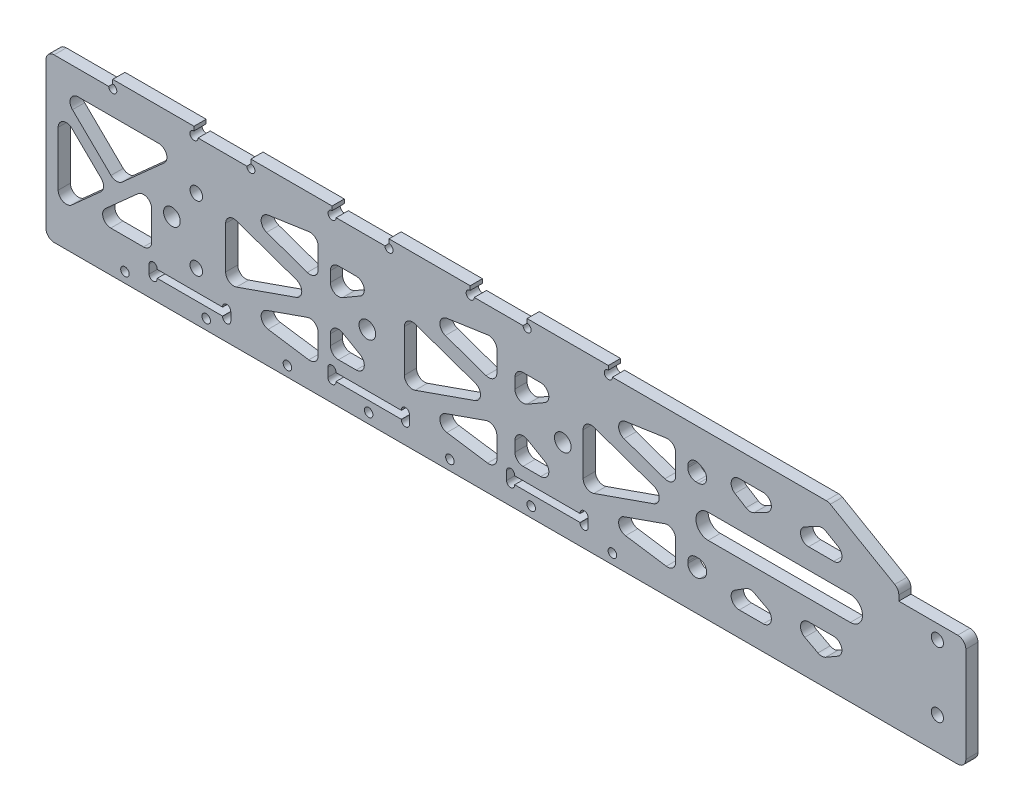
SolidWorks part; units mm, degrees
material "Thornel Mat VMA"
ref_plane "前视基准面" through (0, 0, 0) normal (0, 0, 1) x (1, 0, 0)
ref_plane "上视基准面" through (0, 0, 0) normal (0, 1, 0) x (1, 0, 0)
ref_plane "右视基准面" through (0, 0, 0) normal (1, 0, 0) x (0, 0, -1)
sketch "草图1" plane through (0, 0, 0) normal (0, 0, 1) x (1, 0, 0)
  line L1 (-137.215, -20) -> (137.215, -20)
  line L2 (-137.215, -20) -> (-137.215, 20)
  line L3 (-137.215, 20) -> (137.215, 20)
  line L4 (137.215, -20) -> (137.215, 20)
  line L5 (-137.215, -20) -> (137.215, 20) construction
  line L6 (-137.215, 20) -> (137.215, -20) construction
  point P0 (0, 0)
  dimension "D1" = 274.43
  dimension "D2" = 40
extrude "凸台-拉伸1" add sketch "草图1" along normal blind 3
sketch "草图2" plane through (0, 0, 0) normal (0, 0, 1) x (1, 0, 0)
  line L0 (-157.1827, 0) -> (155.6526, 0) construction
  line L1 (-137.215, -20) -> (-153.215, -20)
  line L2 (-137.215, -20) -> (-137.215, 7.5)
  line L3 (-137.215, 7.5) -> (-153.215, 7.5)
  line L4 (-153.215, -20) -> (-153.215, 7.5)
  line L5 (137.215, -20) -> (153.215, -20)
  line L6 (137.215, -20) -> (137.215, 7.5)
  line L7 (137.215, 7.5) -> (153.215, 7.5)
  line L8 (153.215, -20) -> (153.215, 7.5)
  dimension "D1" = 16
  dimension "D2" = 16
  dimension "D3" = 27.5
  dimension "D4" = 27.5
extrude "凸台-拉伸2" add sketch "草图2" along normal blind 3
sketch "草图3" plane through (0, 0, 3) normal (0, 0, 1) x (1, 0, 0)
  line L0 (-137.215, 20) -> (-137.215, 7.5) construction
  line L1 (-212.4147, 0) -> (176.0969, 0) construction
  line L2 (0, -57.7717) -> (0, 69.9209) construction
  line L3 (212.4147, 0) -> (-176.0969, 0) construction
  line L7 (-212.4147, 0) -> (176.0969, 0) construction
  line L8 (212.4147, 0) -> (-176.0969, 0) construction
  circle A0 centre (-146.215, -12) radius 1.5
  circle A1 centre (-146.215, 4) radius 1.5
  circle A4 centre (-102.215, 0) radius 4.5
  circle A7 centre (146.215, 4) radius 1.5
  circle A8 centre (146.215, -12) radius 1.5
  circle A9 centre (114.785, 0) radius 3
  dimension "D1" = 3
  dimension "D2" = 3
  dimension "D7" = 9
  dimension "D9" = 217
  dimension "D8" = 6
  dimension "D3" = 9
  dimension "D4" = 16
  dimension "D5" = 4
  dimension "D6" = 44
extrude "切除-拉伸1" cut sketch "草图3" against normal through all
sketch "草图6" plane through (0, 0, 3) normal (0, 0, 1) x (1, 0, 0)
  line L0 (-137.215, 7.5) -> (-153.215, 7.5) construction
  line L1 (-137.215, 20) -> (-136.715, 20)
  line L2 (-137.215, 20) -> (-137.215, 7.5)
  line L3 (-137.215, 7.5) -> (-136.715, 7.5)
  line L4 (-136.715, 20) -> (-136.715, 7.5)
  line L5 (137.215, 20) -> (136.715, 20)
  line L6 (137.215, 20) -> (137.215, 7.5)
  line L7 (137.215, 7.5) -> (136.715, 7.5)
  line L8 (136.715, 20) -> (136.715, 7.5)
  line L9 (153.215, 7.5) -> (137.215, 7.5) construction
  dimension "D1" = 0.5
  dimension "D2" = 0.5
  dimension "D3" = 0
  dimension "D4" = 0
extrude "切除-拉伸4" cut sketch "草图6" against normal blind 10
sketch "草图13" plane through (0, 0, 3) normal (0, 0, 1) x (1, 0, 0)
  line L0 (89.785, 0) -> (124.785, 0) construction
  line L1 (89.785, 3) -> (124.785, 3)
  line L2 (89.785, -3) -> (124.785, -3)
  arc A0 (89.785, 3) -> (89.785, -3) centre (89.785, 0) ccw
  arc A1 (124.785, -3) -> (124.785, 3) centre (124.785, 0) ccw
  circle A2 centre (114.785, 0) radius 3 construction
  point P3 (107.285, 0)
  dimension "D1" = 3
  dimension "D2" = 10
  dimension "D3" = 25
extrude "切除-拉伸10" cut sketch "草图13" against normal blind 10
sketch "草图14" plane through (0, 0, 3) normal (0, 0, 1) x (1, 0, 0)
  line L0 (-73.215, 20) -> (-73.215, -20)
  line L1 (136.715, 20) -> (-136.715, 20) construction
  line L2 (-153.215, -20) -> (153.215, -20) construction
  line L3 (-73.215, -20) -> (-153.215, -20)
  line L4 (-153.215, -20) -> (-153.215, 20)
  line L5 (-153.215, 20) -> (-73.215, 20)
  dimension "D1" = 80
extrude "切除-拉伸11" cut sketch "草图14" against normal blind 10
sketch "草图15" plane through (0, 0, 3) normal (0, 0, 1) x (1, 0, 0)
  line L0 (-62.2235, 0) -> (39.7809, 0) construction
  line L1 (-73.215, -20) -> (153.215, -20) construction
  line L2 (-73.215, -20) -> (-73.215, 20) construction
  line L3 (0, 0) -> (0, -20) construction
  line L4 (5.8925, 0) -> (5.8925, -4.9483) construction
  circle A0 centre (-42.215, 0) radius 2.05
  circle A1 centre (0, 0) radius 2.05 construction
  circle A4 centre (54, 0) radius 2.05
  circle A5 centre (5.8925, 0) radius 2.05
  dimension "D2" = 4.1
  dimension "D5" = 4.1
  dimension "D1" = 20
  dimension "D3" = 31
  dimension "D4" = 54
extrude "切除-拉伸12" cut sketch "草图15" against normal blind 10
sketch "草图16" plane through (0, 0, 0) normal (0, 0, -1) x (-1, 0, 0)
  circle A0 centre (-66.215, -17.5) radius 1.05
  circle A1 centre (-46.215, -17.5) radius 1.05
  circle A2 centre (-26.215, -17.5) radius 1.05
  circle A3 centre (-6.215, -17.5) radius 1.05
  circle A4 centre (13.785, -17.5) radius 1.05
  circle A5 centre (33.785, -17.5) radius 1.05
  circle A6 centre (53.785, -17.5) radius 1.05
  dimension "D1" = 2.1
extrude "切除-拉伸13" cut sketch "草图16" against normal blind 10
sketch "草图17" plane through (0, 0, 0) normal (0, 0, -1) x (-1, 0, 0)
  line L0 (-65.215, 20) -> (-65.215, 22)
  line L1 (-136.715, 20) -> (73.215, 20) construction
  line L2 (-65.215, 22) -> (-45.215, 22)
  line L3 (-45.215, 22) -> (-45.215, 20)
  line L4 (-45.215, 20) -> (-65.215, 20)
  line L5 (-75.215, 22) -> (-75.215, 20) construction
  line L6 (-21.215, 22) -> (-21.215, 7.5304) construction
  line L7 (-73.215, 22) -> (30.785, 22) construction
  line L9 (-11.215, 20) -> (-31.215, 20)
  line L10 (-31.215, 20) -> (-31.215, 22)
  line L11 (-31.215, 22) -> (-11.215, 22)
  line L12 (-11.215, 22) -> (-11.215, 20)
  line L13 (2.785, 20) -> (22.785, 20)
  line L14 (2.785, 22) -> (2.785, 20)
  line L15 (22.785, 22) -> (2.785, 22)
  line L16 (22.785, 20) -> (22.785, 22)
  line L17 (36.785, 20) -> (56.785, 20)
  line L18 (56.785, 22) -> (36.785, 22)
  line L19 (36.785, 22) -> (36.785, 20)
  line L20 (56.785, 20) -> (56.785, 22)
  dimension "D1" = 10
  dimension "D2" = 20
  dimension "D3" = 2
  dimension "D5" = 10
  dimension "D6" = 2
  dimension "D7" = 14
  dimension "D4" = 2
extrude "凸台-拉伸3" add sketch "草图17" against normal blind 3
sketch "草图18" plane through (0, 0, 0) normal (0, 0, -1) x (-1, 0, 0)
  line L0 (27.735, -12.95) -> (47.835, -12.95)
  line L1 (-60.265, -12.95) -> (-40.165, -12.95)
  line L2 (-60.265, -12.95) -> (-60.265, -15.05)
  line L3 (-60.265, -15.05) -> (-40.165, -15.05)
  line L4 (-40.165, -12.95) -> (-40.165, -15.05)
  line L5 (-60.265, -12.95) -> (-40.165, -15.05) construction
  line L6 (-60.265, -15.05) -> (-40.165, -12.95) construction
  line L7 (27.735, -15.05) -> (47.835, -15.05)
  line L8 (-40.165, -12.95) -> (-40.165, -15.05) construction
  line L9 (47.835, -12.95) -> (47.835, -15.05)
  line L13 (-16.265, -12.95) -> (3.835, -12.95)
  line L14 (-16.265, -15.05) -> (3.835, -15.05)
  line L15 (3.835, -12.95) -> (3.835, -15.05)
  line L16 (-16.265, -12.95) -> (-16.265, -15.05)
  line L17 (27.735, -12.95) -> (27.735, -15.05)
  point P0 (-50.215, -14)
  dimension "D2" = 44
extrude "切除-拉伸14" cut sketch "草图18" against normal through all
sketch "草图19" plane through (0, 0, 0) normal (0, 0, -1) x (-1, 0, 0)
  line L0 (-40.165, -12.95) -> (-60.265, -12.95) construction
  line L1 (-60.265, -15.05) -> (-40.165, -15.05) construction
  circle A0 centre (-59.265, -12.95) radius 1
  circle A1 centre (-59.265, -15.05) radius 1
  circle A2 centre (-41.165, -12.95) radius 1
  circle A3 centre (-41.165, -15.05) radius 1
  circle A4 centre (-15.265, -12.95) radius 1
  circle A5 centre (-15.265, -15.05) radius 1
  circle A6 centre (2.835, -12.95) radius 1
  circle A7 centre (2.835, -15.05) radius 1
  circle A8 centre (28.735, -12.95) radius 1
  circle A9 centre (28.735, -15.05) radius 1
  circle A10 centre (46.835, -12.95) radius 1
  circle A11 centre (46.835, -15.05) radius 1
  dimension "D1" = 2
  dimension "D3" = 44
  dimension "D2" = 3
extrude "切除-拉伸15" cut sketch "草图19" against normal blind 3
chamfer "倒角1" distance 10 angle 60 1 edges at (136.715, 20, 1.5) first distance on face at (136.715, 13.75, 1.5)
sketch "草图21" plane through (0, 0, 0) normal (0, 0, -1) x (-1, 0, 0)
  line L0 (-86.785, 0) -> (73.215, 0) construction
  line L1 (73.215, 20) -> (73.215, -20) construction
  line L8 (-63.8825, -14) -> (-59, -8) construction
  line L15 (-81.785, 14) -> (-59, 14) construction
  line L16 (-81.785, 14) -> (-81.785, -14) construction
  line L18 (-81.785, -14) -> (-59, -14) construction
  line L19 (-59, 14) -> (-59, -14) construction
  line L20 (-81.785, 14) -> (-59, -14) construction
  line L21 (-81.785, -14) -> (-59, 14) construction
  line L23 (-63.8825, 14) -> (-59, 8) construction
  line L25 (73.215, -20) -> (-153.215, -20) construction
  line L26 (-59, -8) -> (-81.785, 0)
  line L27 (-81.785, 0) -> (-59, 8)
  line L32 (-61.4412, -11) -> (-81.785, -14)
  line L33 (-81.785, -14) -> (-81.785, -3.8571)
  line L35 (-81.785, 14) -> (-81.785, 3.8571)
  line L36 (-81.785, 3.8571) -> (-61.4412, 11)
  line L39 (-61.4412, 11) -> (-81.785, 14)
  line L41 (-81.785, -3.8571) -> (-61.4412, -11)
  line L43 (-59, -8) -> (-59, 8)
  line L45 (-128.1773, 8) -> (-117.785, 14) construction
  line L46 (-117.785, 14) -> (-84.785, 14) construction
  line L47 (-84.785, 14) -> (-84.785, 8) construction
  line L48 (-84.785, 8) -> (-128.1773, 8) construction
  line L49 (-119.3945, 20) -> (-136.715, 10) construction
  line L50 (-119.3945, 20) -> (-65.215, 20) construction
  line L51 (-128.1773, 8) -> (-117.785, 14)
  line L52 (-117.785, 14) -> (-106.4812, 8)
  line L53 (-106.4812, 8) -> (-128.1773, 8)
  line L54 (-111.3862, 14) -> (-100.0824, 8)
  line L55 (-100.0824, 8) -> (-90.4564, 14)
  line L56 (-90.4564, 14) -> (-111.3862, 14)
  line L57 (-84.785, 14) -> (-94.411, 8)
  line L58 (-94.411, 8) -> (-84.785, 8)
  line L59 (-84.785, 8) -> (-84.785, 14)
  line L60 (-94.411, -8) -> (-84.785, -8)
  line L61 (-84.785, -14) -> (-94.411, -8)
  line L62 (-84.785, -8) -> (-84.785, -14)
  line L63 (-100.0824, -8) -> (-90.4564, -14)
  line L64 (-111.3862, -14) -> (-100.0824, -8)
  line L65 (-90.4564, -14) -> (-111.3862, -14)
  line L66 (-106.4812, -8) -> (-128.1773, -8)
  line L67 (-117.785, -14) -> (-106.4812, -8)
  line L68 (-128.1773, -8) -> (-117.785, -14)
  line L69 (-15, -8) -> (-15, 8)
  line L70 (-37.785, 0) -> (-15, 8)
  line L71 (-15, -8) -> (-37.785, 0)
  line L72 (-17.4413, 11) -> (-37.785, 14)
  line L73 (-37.785, 14) -> (-37.785, 3.8571)
  line L74 (-37.785, 3.8571) -> (-17.4413, 11)
  line L75 (-37.785, -3.8571) -> (-17.4413, -11)
  line L76 (-17.4413, -11) -> (-37.785, -14)
  line L77 (-37.785, -14) -> (-37.785, -3.8571)
  line L78 (29, -8) -> (29, 8)
  line L79 (6.215, 0) -> (29, 8)
  line L80 (29, -8) -> (6.215, 0)
  line L81 (26.5587, 11) -> (6.215, 14)
  line L82 (6.215, 14) -> (6.215, 3.8571)
  line L83 (6.215, 3.8571) -> (26.5587, 11)
  line L84 (6.215, -3.8571) -> (26.5587, -11)
  line L85 (26.5587, -11) -> (6.215, -14)
  line L86 (6.215, -14) -> (6.215, -3.8571)
  line L87 (-56, 10) -> (-42.2187, 2)
  line L88 (-42.2187, 2) -> (-42.2187, 10)
  line L89 (-42.2187, 10) -> (-56, 10)
  line L90 (-42.2187, -2) -> (-42.2187, -10)
  line L91 (-56, -10) -> (-42.2187, -2)
  line L92 (-42.2187, -10) -> (-56, -10)
  line L93 (-45.215, 20) -> (-31.215, 20) construction
  line L94 (3.215, -2) -> (3.215, -10)
  line L95 (3.215, -10) -> (-10.5663, -10)
  line L96 (-10.5663, -10) -> (3.215, -2)
  line L97 (3.215, 10) -> (-10.5663, 10)
  line L98 (-10.5663, 10) -> (3.215, 2)
  line L99 (3.215, 2) -> (3.215, 10)
  line L100 (40.215, 14) -> (55.8771, 0)
  line L101 (55.8771, 0) -> (70.215, 14)
  line L102 (70.215, 14) -> (40.215, 14)
  line L106 (70.215, 9.8071) -> (58.1189, -2.0039)
  line L107 (58.1189, -2.0039) -> (70.215, -12.8164)
  line L108 (70.215, -12.8164) -> (70.215, 9.8071)
  line L109 (56.785, 20) -> (73.215, 20) construction
  line L114 (47.215, 3.719) -> (47.215, -9.95)
  line L115 (47.215, -9.95) -> (62.5068, -9.95)
  line L116 (47.215, 3.719) -> (62.5068, -9.95)
  line L117 (45.835, -12.95) -> (29.735, -12.95) construction
  arc A0 (-89.785, -3) -> (-89.785, 3) centre (-89.785, 0) ccw construction
  circle A1 centre (-54, 0) radius 2.05 construction
  circle A2 centre (42.215, 0) radius 2.05 construction
  point P7 (-70.3925, 0)
  point P93 (63.046, 7)
  dimension "D1" = 5
  dimension "D2" = 5
  dimension "D3" = 6
  dimension "D4" = 6
  dimension "D5" = 6
  dimension "D6" = 8
  dimension "D7" = 6
  dimension "D8" = 3
  dimension "D10" = 3
  dimension "D11" = 3
  dimension "D12" = 3
  dimension "D13" = 44
  dimension "D14" = 4.4337
  dimension "D15" = 3
  dimension "D16" = 8
  dimension "D17" = 10
  dimension "D19" = 3
  dimension "D20" = 3
  dimension "D21" = 6
  dimension "D22" = 30
  dimension "D23" = 3
  dimension "D24" = 5
  dimension "D25" = 3
  dimension "D26" = 3
  dimension "D18" = 2
extrude "切除-拉伸16" cut sketch "草图21" against normal through all
fillet "圆角1" radius 2 66 edges at (81.785, 3.8571, 1.5) (81.785, 14, 1.5) (61.4412, 11, 1.5) (-47.215, -9.95, 1.5) (-47.215, 3.719, 1.5) (-62.5068, -9.95, 1.5) (-3.215, -10, 1.5) (10.5663, -10, 1.5) (-3.215, -2, 1.5) (-55.8771, 0, 1.5) (-40.215, 14, 1.5) (-70.215, 14, 1.5) (-3.215, 10, 1.5) (-3.215, 2, 1.5) (10.5663, 10, 1.5) (-58.1189, -2.0039, 1.5) (-70.215, 9.8071, 1.5) (-70.215, -12.8164, 1.5) (17.4413, -11, 1.5) (37.785, -14, 1.5) (37.785, -3.8571, 1.5) (15, 8, 1.5) (15, -8, 1.5) (37.785, 0, 1.5) (42.2187, 2, 1.5) (56, 10, 1.5) (42.2187, 10, 1.5) (17.4413, 11, 1.5) (37.785, 3.8571, 1.5) (37.785, 14, 1.5) (42.2187, -10, 1.5) (56, -10, 1.5) (42.2187, -2, 1.5) (-29, 8, 1.5) (-29, -8, 1.5) (-6.215, 0, 1.5) (-26.5587, -11, 1.5) (-6.215, -14, 1.5) (-6.215, -3.8571, 1.5) (-26.5587, 11, 1.5) (-6.215, 3.8571, 1.5) (-6.215, 14, 1.5) (81.785, 0, 1.5) (59, 8, 1.5) (59, -8, 1.5) (61.4412, -11, 1.5) (81.785, -14, 1.5) (81.785, -3.8571, 1.5) (106.4812, 8, 1.5) (100.0824, 8, 1.5) (111.3862, 14, 1.5) (90.4564, 14, 1.5) (90.4564, -14, 1.5) (111.3862, -14, 1.5) (100.0824, -8, 1.5) (128.1773, -8, 1.5) (106.4812, -8, 1.5) (117.785, -14, 1.5) (84.785, -8, 1.5) (84.785, -14, 1.5) (94.411, -8, 1.5) (94.411, 8, 1.5) (84.785, 14, 1.5) (84.785, 8, 1.5) (117.785, 14, 1.5) (128.1773, 8, 1.5)
fillet "圆角2" radius 2 6 edges at (-73.215, 20, 1.5) (-73.215, -20, 1.5) (119.3945, 20, 1.5) (136.715, 10, 1.5) (153.215, 7.5, 1.5) (153.215, -20, 1.5)
sketch "草图22" plane through (0, 0, 0) normal (0, 0, -1) x (-1, 0, 0)
  line L0 (36.215, 20) -> (36.215, -12.95) construction
  line L1 (22.785, 20) -> (36.785, 20) construction
  line L2 (45.835, -12.95) -> (29.735, -12.95) construction
  circle A0 centre (42.215, 0) radius 2.05 construction
  circle A1 centre (36.215, 8) radius 1.55
  circle A2 centre (36.215, -8) radius 1.55
  dimension "D2" = 3.1
  dimension "D3" = 3.1
  dimension "D5" = 8
  dimension "D1" = 6
  dimension "D4" = 8
extrude "切除-拉伸17" cut sketch "草图22" against normal blind 10
sketch "草图24" plane through (0, 0, 0) normal (0, 0, -1) x (-1, 0, 0)
  line L0 (-58.265, -12.95) -> (-42.165, -12.95)
  line L1 (-58.265, -12.95) -> (-58.265, -13.05)
  line L2 (-42.165, -12.95) -> (-42.165, -13.05)
  line L3 (-58.265, -13.05) -> (-42.165, -13.05)
  line L4 (-58.265, -15.05) -> (-42.165, -15.05)
  line L5 (-58.265, -15.05) -> (-58.265, -14.95)
  line L6 (-42.165, -15.05) -> (-42.165, -14.95)
  line L7 (-58.265, -14.95) -> (-42.165, -14.95)
  line L8 (-14.265, -12.95) -> (1.835, -12.95)
  line L9 (-14.265, -12.95) -> (-14.265, -13.05)
  line L10 (1.835, -12.95) -> (1.835, -13.05)
  line L11 (-14.265, -13.05) -> (1.835, -13.05)
  line L12 (-14.265, -15.05) -> (1.835, -15.05)
  line L13 (-14.265, -15.05) -> (-14.265, -14.95)
  line L14 (1.835, -15.05) -> (1.835, -14.95)
  line L15 (-14.265, -14.95) -> (1.835, -14.95)
  line L16 (29.735, -12.95) -> (45.835, -12.95)
  line L17 (29.735, -12.95) -> (29.735, -13.05)
  line L18 (45.835, -12.95) -> (45.835, -13.05)
  line L19 (29.735, -13.05) -> (45.835, -13.05)
  line L20 (29.735, -15.05) -> (45.835, -15.05)
  line L21 (29.735, -15.05) -> (29.735, -14.95)
  line L22 (45.835, -15.05) -> (45.835, -14.95)
  line L23 (29.735, -14.95) -> (45.835, -14.95)
  line L24 (29.735, -15.05) -> (45.835, -15.05) construction
  arc A0 (29.735, -12.95) -> (27.735, -12.95) centre (28.735, -12.95) ccw construction
  arc A1 (27.735, -15.05) -> (29.735, -15.05) centre (28.735, -15.05) ccw construction
  dimension "D1" = 0.1
  dimension "D2" = 0.1
  dimension "D3" = 0.1
  dimension "D4" = 0.1
  dimension "D5" = 0.1
  dimension "D6" = 0.1
extrude "凸台-拉伸4" add sketch "草图24" against normal up to surface (3 mm away) up to face at (-37.765, 8, 3)
sketch "草图25" plane through (0, 0, 0) normal (0, 0, -1) x (-1, 0, 0)
  circle A0 centre (-65.215, 20) radius 1
  circle A1 centre (-45.215, 20) radius 1
  circle A2 centre (-31.215, 20) radius 1
  circle A3 centre (-11.215, 20) radius 1
  circle A4 centre (2.785, 20) radius 1
  circle A5 centre (22.785, 20) radius 1
  circle A6 centre (36.785, 20) radius 1
  circle A7 centre (56.785, 20) radius 1
  dimension "D1" = 2
  dimension "D2" = 2
  dimension "D3" = 2
  dimension "D4" = 2
  dimension "D5" = 2
  dimension "D6" = 2
  dimension "D7" = 2
  dimension "D8" = 2
extrude "切除-拉伸18" cut sketch "草图25" against normal blind 10
